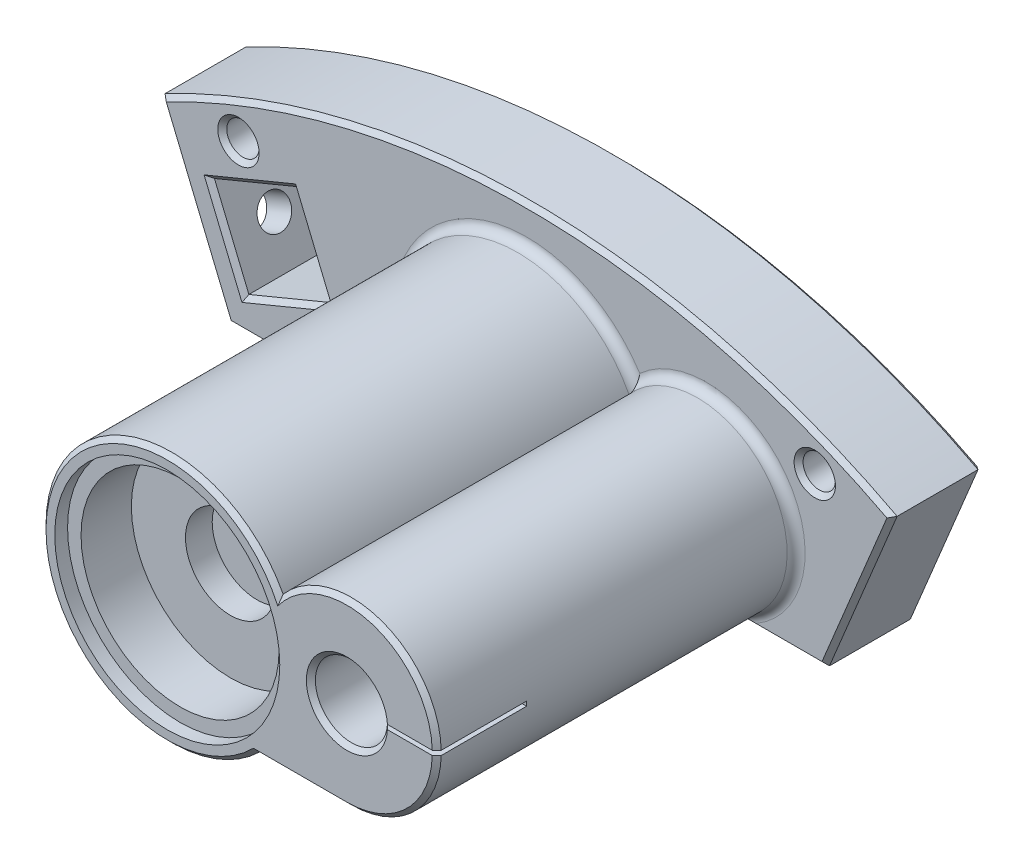
SolidWorks part; units mm, degrees
ref_plane "Front Plane" through (0, 0, 0) normal (0, 0, 1) x (1, 0, 0)
ref_plane "Top Plane" through (0, 0, 0) normal (0, 1, 0) x (1, 0, 0)
ref_plane "Right Plane" through (0, 0, 0) normal (1, 0, 0) x (0, 0, -1)
sketch "Sketch1" plane through (0, 0, 0) normal (0, 0, 1) x (1, 0, 0)
  line L0 (-46.9014, 0) -> (43.5211, 0) construction
  line L1 (0, 38.5211) -> (0, -80.4339) construction
  line L2 (-33.5349, -69.25) -> (36.7559, -69.25) construction
  line L3 (0, -69.25) -> (-37.9703, 22.4183) construction
  line L4 (-40.7467, 8.1836) -> (-33.2148, -10)
  line L5 (-25.9885, 6.5901) -> (-35.2504, 2.7537)
  line L6 (-35.2504, 2.7537) -> (-31.414, -6.5082)
  line L7 (-31.414, -6.5082) -> (-22.1521, -2.6718)
  line L8 (-22.1521, -2.6718) -> (-25.9885, 6.5901)
  line L9 (-33.2148, -10) -> (-9.798, -10)
  line L10 (33.2148, -10) -> (9.798, -10)
  line L11 (40.7467, 8.1836) -> (33.2148, -10)
  line L12 (20, 7.6656) -> (20, -13.8845) construction
  circle A1 centre (-28.7013, 0.041) radius 5.0125 construction
  arc A2 (40.7467, 8.1836) -> (-40.7467, 8.1836) centre (0, -69.25) ccw
  arc A5 (-9.798, -10) -> (9.798, -10) centre (0, 0) ccw
  circle A6 centre (0, 0) radius 5
  circle A7 centre (-32.0765, 8.1894) radius 1.8
  circle A8 centre (32.0765, 8.1894) radius 1.8
  circle A9 centre (20, 0) radius 3
  point P32 (0, -14)
  dimension "D2" = 20
  dimension "D7" = 75
  dimension "D8" = 175
  dimension "D9" = 3
  dimension "D10" = 14
  dimension "D12" = 10
  dimension "D13" = 3.6
  dimension "D14" = 32.0765
  dimension "D16" = 6
  dimension "D3" = 69.25
  dimension "D4" = 22.5
  dimension "D5" = 10.025
  dimension "D6" = 90
  dimension "D11" = 10
extrude "Boss-Extrude1" add sketch "Sketch1" along normal blind 10
sketch "Sketch3" plane through (0, 0, 0) normal (0, 0, -1) x (-1, 0, 0)
  circle A0 centre (0, 0) radius 11.025
  dimension "D1" = 22.05
sketch "Sketch4" plane through (0, 0, 0) normal (0, 0, -1) x (-1, 0, 0)
  circle A0 centre (0, 0) radius 12.525
  dimension "D1" = 25.05
sketch "Sketch5" plane through (-29.1145, -12.0596, 0) normal (0.9239, 0.3827, 0) x (0, 0, -1)
  line L5 (-10, 16.0338) -> (0, 16.0338) construction
  line L6 (0, 16.0338) -> (0, 6.0088) construction
  circle A0 centre (-4.75, 11.0188) radius 1.8
  dimension "D1" = 3.6
  dimension "D2" = 5.015
  dimension "D3" = 4.75
extrude "Cut-Extrude4" cut sketch "Sketch5" against normal blind 10
sketch "Sketch6" plane through (0, 0, 10) normal (0, 0, 1) x (1, 0, 0)
  line L1 (9.798, -10) -> (20, -10)
  line L2 (0, 22.1581) -> (0, -16.2187) construction
  arc A2 (12.4, 6.4992) -> (9.798, -10) centre (0, 0) ccw
  arc A3 (20, -10) -> (12.4, 6.4992) centre (20, 0) ccw
  circle A4 centre (0, 0) radius 5 construction
  circle A5 centre (0, 0) radius 5
  circle A6 centre (20, 0) radius 3 construction
  circle A7 centre (20, 0) radius 3
  dimension "D1" = 28
  dimension "D2" = 20
  dimension "D3" = 20
extrude "Boss-Extrude3" add sketch "Sketch6" along normal blind 40
sketch "Sketch7" plane through (0, 0, 50) normal (0, 0, 1) x (1, 0, 0)
  circle A0 centre (0, 0) radius 11.025
  dimension "D1" = 22.05
extrude "Cut-Extrude5" cut sketch "Sketch7" against normal blind 7.025
sketch "Sketch8" plane through (0, 0, 50) normal (0, 0, 1) x (1, 0, 0)
  circle A0 centre (0, 0) radius 12.525
  dimension "D1" = 25.05
extrude "Cut-Extrude6" cut sketch "Sketch8" against normal blind 1.425
sketch "Sketch9" plane through (0, 0, 50) normal (0, 0, 1) x (1, 0, 0)
  line L0 (-15.573, 0) -> (48.0602, 0) construction
  line L1 (24.0047, 0.25) -> (29.9969, 0.25)
  line L2 (24.0047, -0.25) -> (29.9969, -0.25)
  arc A0 (24.0047, 0.25) -> (24.0047, -0.25) centre (20, 0) ccw
  arc A1 (20, -10) -> (12.4, 6.4992) centre (20, 0) ccw construction
  arc A2 (29.9969, -0.25) -> (29.9969, 0.25) centre (20, 0) ccw
  dimension "D1" = 8.025
  dimension "D2" = 0.25
extrude "Cut-Extrude7" cut sketch "Sketch9" against normal blind 10
chamfer "Chamfer1" distance 0.5 angle 57.296 16 edges at (30.2765, 8.1894, 10) (-33.3322, -1.8772, 10) (-26.7831, -4.59, 10) (-24.0703, 1.9592, 10) (-30.6195, 4.6719, 10) (-30.2765, 8.1894, 10) (26.6074, -10, 10) (36.9808, -0.9082, 10) (0, 18.25, 10) (-21.5064, -10, 10) (-36.9808, -0.9082, 10) (15.9875, 0, 50) (26.9821, -7.1589, 50) (14.899, -10, 50) (23.3466, 9.4234, 50) (-13.8291, 2.1809, 50)
fillet "Fillet1" radius 1 2 edges at (28.307, 5.5672, 10) (-8.0693, 11.4406, 10)
sketch "Sketch10" plane through (0, 0, 0) normal (0, 0, -1) x (-1, 0, 0)
  circle A0 centre (0, 0) radius 5 construction
  circle A1 centre (0, 0) radius 5
  circle A2 centre (-20, 0) radius 3 construction
  circle A3 centre (-20, 0) radius 3
extrude "Boss-Extrude4" add sketch "Sketch10" against normal blind 40
chamfer "Chamfer2" distance 0.5 angle 45 12 edges at (30.2765, 8.1894, 0) (-30.2765, 8.1894, 0) (-26.7831, -4.59, 0) (-33.3322, -1.8772, 0) (-30.6195, 4.6719, 0) (-24.0703, 1.9592, 0) (0, 18.25, 0) (-36.9808, -0.9082, 0) (-21.5064, -10, 0) (0, -14, 0) (21.5064, -10, 0) (36.9808, -0.9082, 0)
